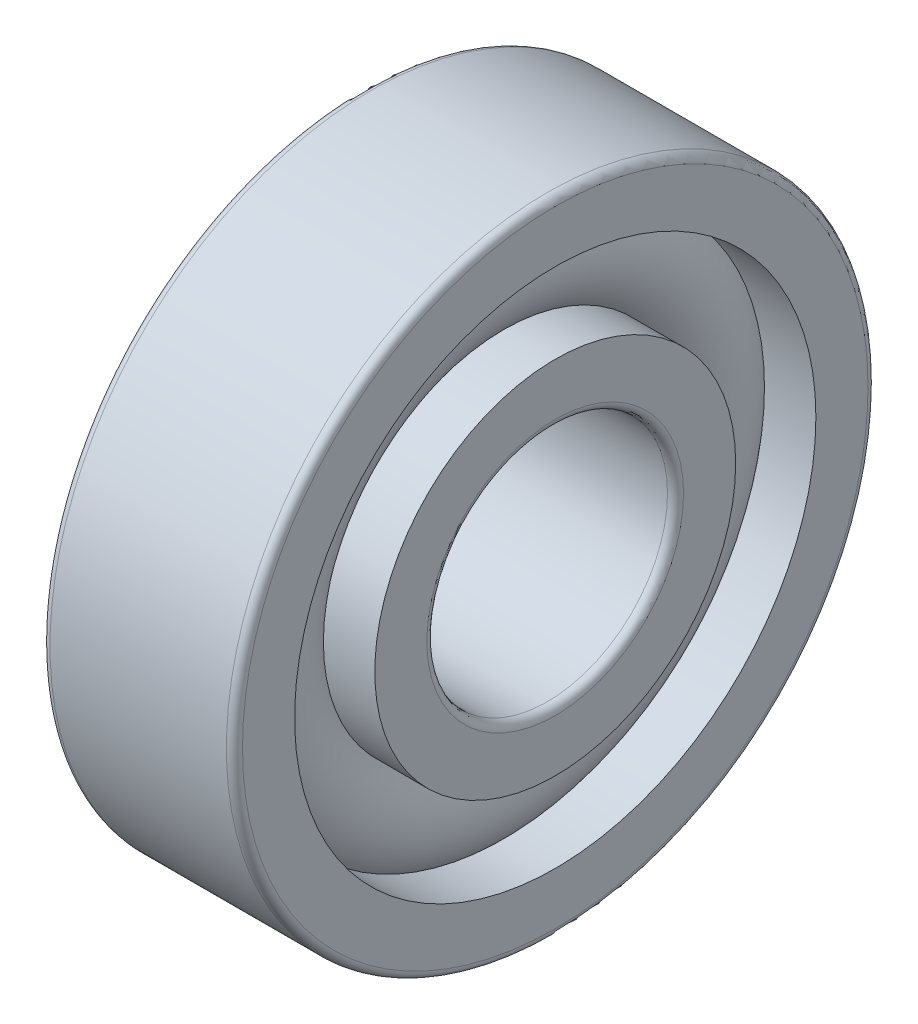
SolidWorks part; units mm, degrees
ref_plane "Plane1" through (0, 0, 0) normal (0, 0, 1) x (1, 0, 0)
ref_plane "Plane2" through (0, 0, 0) normal (0, 1, 0) x (1, 0, 0)
ref_plane "Plane3" through (0, 0, 0) normal (1, 0, 0) x (0, 0, -1)
other "Configuration Table"
sketch "Clipboard" plane through (0, 0, 0) normal (0, 0, 1) x (1, 0, 0)
  line L0 (-10, 0) -> (10, 0) construction
  line L1 (0, 0) -> (22.3471, -0.7804)
  line L2 (0, 0) -> (1.3742, 0.048)
  line L3 (0, 0) -> (22.3471, -0.7804)
  line L4 (0, 0) -> (-22.3573, -0.3902)
  dimension "BallCLRad" = 1.375
  dimension "Count" = 2
sketch "CagSpiSke" plane through (0, 0, 0) normal (0, 0, 1) x (1, 0, 0)
  line L0 (0.0375, 1.3125) -> (0.0375, 1.4375)
  line L1 (0.0375, 1.4375) -> (-0.0375, 1.4375)
  line L2 (-0.0375, 1.4375) -> (-0.0375, 1.3125)
  line L3 (-0.0375, 1.3125) -> (0.0375, 1.3125)
  line L4 (-20.6375, 0) -> (20.6375, 0) construction
  line L5 (0, 0) -> (0, 23.7692) construction
  dimension "OD" = 2.875
  dimension "ID" = 2.625
revolve "CageSpine" add sketch "CagSpiSke" angle 0.001 about L4 reverse direction yes
ref_axis "Axis1" through (-50, 0, 0) along (1, 0, 0)
sketch "CagBalSke" plane through (0, 0, 0) normal (0, 0, 1) x (1, 0, 0)
  line L0 (-0.4125, 1.375) -> (0.4125, 1.375)
  line L1 (-1.905, 1.375) -> (1.905, 1.375) construction
  line L2 (-10, 0) -> (10, 0) construction
  line L3 (0, 0) -> (0, 24) construction
  arc A0 (0.4125, 1.375) -> (-0.4125, 1.375) centre (0, 1.375) cw
  dimension "BallCLRad" = 1.375
revolve "CageBall" [suppressed] add sketch "CagBalSke" angle 360 about L1 reverse direction yes
pattern_circular "CageBalls" [suppressed] count 2 every 180 about axis through (-50, 0, 0) along (1, 0, 0)
sketch "CagTrmODSke" plane through (0, 0, 0) normal (0, 0, 1) x (1, 0, 0)
  line L0 (0.4135, 1.4375) -> (0.4135, 1.7885)
  line L1 (0.4135, 1.7885) -> (-0.4135, 1.7885)
  line L2 (-0.4135, 1.7885) -> (-0.4135, 1.4375)
  line L3 (-0.4135, 1.4375) -> (0.4135, 1.4375)
  line L4 (-20.6375, 0) -> (20.6375, 0) construction
  line L5 (0, 0) -> (0, 25) construction
  dimension "Width" = 0.827
  dimension "ID" = 2.875
  dimension "OD" = 3.577
revolve "CageTrimOD" [suppressed] cut sketch "CagTrmODSke" angle 360 about L4 reverse direction yes
sketch "CagTrmIDSke" plane through (0, 0, 0) normal (0, 0, 1) x (1, 0, 0)
  line L0 (0.4135, 0.9635) -> (0.4135, 1.3125)
  line L1 (0.4135, 1.3125) -> (-0.4135, 1.3125)
  line L2 (-0.4135, 1.3125) -> (-0.4135, 0.9635)
  line L3 (-0.4135, 0.9635) -> (0.4135, 0.9635)
  line L4 (-20.6375, 0) -> (20.6375, 0) construction
  line L5 (0, 0) -> (0, 25) construction
  dimension "Width" = 0.827
  dimension "ID" = 1.927
  dimension "OD" = 2.625
revolve "CageTrimID" [suppressed] cut sketch "CagTrmIDSke" angle 360 about L4 reverse direction yes
sketch "BalSimSke" plane through (0, 0, 0) normal (0, 0, 1) x (1, 0, 0)
  line L0 (-10, 0) -> (10, 0) construction
  line L1 (-10, 1.375) -> (10, 1.375) construction
  line L2 (0, 0) -> (0, 23) construction
  circle A0 centre (0, 1.375) radius 0.375
  dimension "BallCLRad" = 1.375
  dimension "Ball_diameter" = 0.75
revolve "BallsSimplified" add sketch "BalSimSke" angle 360 about L0
sketch "BalDetSke" plane through (0, 0, 0) normal (0, 0, 1) x (1, 0, 0)
  line L0 (-0.375, 1.375) -> (0.375, 1.375)
  line L1 (-1.905, 1.375) -> (1.905, 1.375) construction
  line L2 (0, 0) -> (0, 25) construction
  arc A0 (0.375, 1.375) -> (-0.375, 1.375) centre (0, 1.375) cw
  dimension "BallCLRad" = 1.375
  dimension "Ball_diameter" = 0.75
revolve "BallDetailed" [suppressed] add sketch "BalDetSke" angle 360 about L1 reverse direction yes
sketch "InnRacSke" plane through (0, 0, 0) normal (0, 0, 1) x (1, 0, 0)
  line L0 (-0.2449, 1.125) -> (-0.6, 1.125)
  line L1 (-0.6, 1.125) -> (-0.6, 0.8)
  line L2 (-0.55, 0.75) -> (0.55, 0.75)
  line L3 (0.6, 0.8) -> (0.6, 1.125)
  line L4 (0.6, 1.125) -> (0.2449, 1.125)
  line L5 (-20.6375, 0) -> (20.6375, 0) construction
  line L6 (0, 0) -> (0, 30) construction
  arc A0 (-0.6, 0.8) -> (-0.55, 0.75) centre (-0.55, 0.8) ccw
  arc A1 (0.55, 0.75) -> (0.6, 0.8) centre (0.55, 0.8) ccw
  arc A2 (0.2449, 1.125) -> (-0.2449, 1.125) centre (0, 1.375) cw
  dimension "BallCLRad" = 1.375
  dimension "Fillet_radius" = 0.05
  dimension "ID" = 1.5
  dimension "OD" = 2.25
  dimension "Width" = 1.2
revolve "InnerRace" add sketch "InnRacSke" angle 360 about L5 reverse direction yes
sketch "OutRacSke" plane through (0, 0, 0) normal (0, 0, 1) x (1, 0, 0)
  line L0 (-0.2449, 1.625) -> (-0.6, 1.625)
  line L1 (-0.6, 1.625) -> (-0.6, 1.95)
  line L2 (-0.55, 2) -> (0.55, 2)
  line L3 (0.6, 1.95) -> (0.6, 1.625)
  line L4 (0.6, 1.625) -> (0.2449, 1.625)
  line L5 (-20.6375, 0) -> (20.6375, 0) construction
  line L6 (0, 0) -> (0, 30) construction
  arc A0 (-0.6, 1.95) -> (-0.55, 2) centre (-0.55, 1.95) cw
  arc A1 (0.55, 2) -> (0.6, 1.95) centre (0.55, 1.95) cw
  arc A2 (0.2449, 1.625) -> (-0.2449, 1.625) centre (0, 1.375) ccw
  dimension "BallCLRad" = 1.375
  dimension "Fillet_radius" = 0.05
  dimension "Width" = 1.2
  dimension "OD" = 3.577
revolve "OuterRace" add sketch "OutRacSke" angle 360 about L5 reverse direction yes
pattern_circular "BallsDetailed" [suppressed] count 2 every 180 about axis through (-50, 0, 0) along (1, 0, 0)
equation "\"BallCLRad@Clipboard\" = ( \"OD@OutRacSke\" + \"ID@InnRacSke\" ) / 4"
equation "\"BallCLRad@BalSimSke\" = \"BallCLRad@Clipboard\""
equation "\"BallCLRad@BalDetSke\" = \"BallCLRad@Clipboard\""
equation "\"BallCLRad@InnRacSke\" = \"BallCLRad@Clipboard\""
equation "\"BallCLRad@OutRacSke\" = \"BallCLRad@Clipboard\""
equation "\"Ball_diameter@InnRacSke\" = \"Ball_diameter@BalDetSke\" - 0.05"
equation "\"Ball_diameter@OutRacSke\" = \"Ball_diameter@BalDetSke\" - 0.05"
equation "\"Ball_diameter@BalSimSke\" = \"Ball_diameter@BalDetSke\""
equation "\"Width@OutRacSke\" = \"Width@InnRacSke\""
equation "\"Fillet_radius@OutRacSke\" = \"Fillet_radius@InnRacSke\""
equation "\"Max_count@Clipboard\" = int( 3.14159265 / atn(( \"Ball_diameter@BalDetSke\" / 2) / sqr( \"BallCLRad@Clipboard\"  *  \"BallCLRad@Clipboard\" - ( \"Ball_diameter@BalDetSke\" / 2) *  ( \"Ball_diameter@BalDetSke\" / 2))))"
equation "\"Max_count@Clipboard\" = ((sgn( \"Max_count@Clipboard\" - \"Count@Clipboard\" )-1)*( \"Max_count@Clipboard\" - \"Count@Clipboard\" ))/-2+ \"Count@Clipboard\""
equation "\"Count@BallsDetailed\" = int( \"Show_count@Clipboard\" ) "
equation "\"Count@BallsDetailed\" = ((sgn( \"Count@BallsDetailed\" - \"Max_count@Clipboard\" )-1)*( \"Count@BallsDetailed\" - \"Max_count@Clipboard\" ))/-2+ \"Max_count@Clipboard\""
equation "\"Count@BallsDetailed\" = ((sgn( \"Count@BallsDetailed\" - \"Min_count@Clipboard\" )+1)*( \"Count@BallsDetailed\" - \"Min_count@Clipboard\"))/2 +\"Min_count@Clipboard\""
equation "\"Angle@BallsDetailed\" = 360.0 / \"Max_count@Clipboard\""
equation "\"BallCLRad@CagBalSke\" = \"BallCLRad@Clipboard\""
equation "\"Count@CageBalls\" = \"Count@BallsDetailed\""
equation "\"Angle@CageBalls\" = \"Angle@BallsDetailed\""
equation "\"Angle@CageSpine\" =  \"Angle@CageBalls\" * ( \"Count@CageBalls\" -1 + int( \"Count@CageBalls\" / \"Max_count@Clipboard\" ) )  + 0.001 -  int( \"Count@CageBalls\" / \"Max_count@Clipboard\" ) * 0.001"
equation "\"Angle@CageSpine\" =  \"Angle@CageSpine\" * int( \"Min_count@Clipboard\" / 2) + int(1 / \"Min_count@Clipboard\")  * 0.001"
equation "\"CageWallOD@CagBalSke\" =  \"Ball_diameter@BalDetSke\" * 1.1"
equation "\"Thickness@CagSpiSke\" =  \"Ball_diameter@BalDetSke\" * 0.1"
equation "\"OD@CagTrmODSke\" = \"BallCLRad@Clipboard\" * 2 + \"CageWallOD@CagBalSke\" + 0.002"
equation "\"ID@CagTrmODSke\" = \"BallCLRad@Clipboard\" * 2 + \"Ball_diameter@BalDetSke\" / 6"
equation "\"OD@CagTrmIDSke\" = \"BallCLRad@Clipboard\" * 2 - \"Ball_diameter@BalDetSke\" / 6"
equation "\"ID@CagTrmIDSke\" = \"BallCLRad@Clipboard\" * 2 - \"CageWallOD@CagBalSke\" + 0.002"
equation "\"OD@CagSpiSke\" = \"ID@CagTrmODSke\""
equation "\"ID@CagSpiSke\" = \"OD@CagTrmIDSke\""
equation "\"Width@CagTrmODSke\" = \"CageWallOD@CagBalSke\" + 0.002"
equation "\"Width@CagTrmIDSke\" = \"CageWallOD@CagBalSke\" + 0.002"
